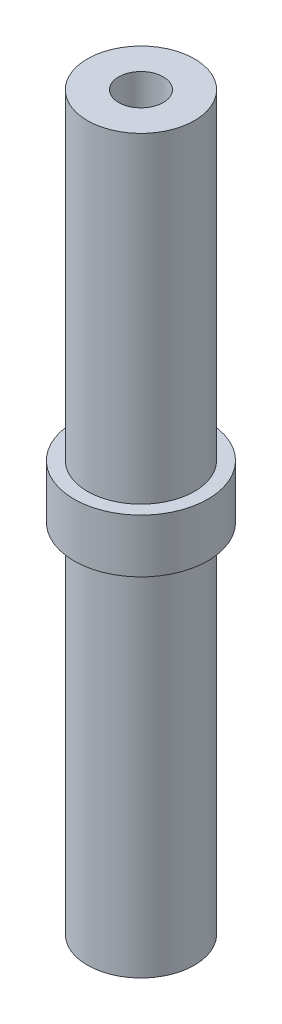
SolidWorks part; units mm, degrees
material "6061-T6 (SS)"
ref_plane "Front Plane" through (0, 0, 0) normal (0, 0, 1) x (1, 0, 0)
ref_plane "Top Plane" through (0, 0, 0) normal (0, 1, 0) x (1, 0, 0)
ref_plane "Right Plane" through (0, 0, 0) normal (1, 0, 0) x (0, 0, -1)
sketch "Sketch1" plane through (0, 0, 0) normal (0, 1, 0) x (1, 0, 0)
  circle A0 centre (0, 0) radius 3
  circle A1 centre (0, 0) radius 2 construction
  dimension "D1" = 6
  dimension "D2" = 4
extrude "Boss-Extrude1" add sketch "Sketch1" along normal blind 20.5 and the other way blind 20.5
sketch "Sketch2" plane through (0, 20.5, 0) normal (0, 1, 0) x (1, 0, 0)
  point P0 (0, 0)
hole_wizard "M3x0.5 Tapped Hole1" positions "Sketch4" profile "Sketch5" tap size "M3x0.5" standard "ANSI Metric"
sketch "Sketch4" plane through (0, 20.5, 0) normal (0, 1, 0) x (1, 0, 0)
  point P0 (0, 0)
sketch "Sketch5" plane through (0, 20.5, 0) normal (1, 0, 0) x (0, 0, 1)
  line L0 (0, 0) -> (0, 8.7511)
  line L1 (0, 8.7511) -> (1.25, 8)
  line L2 (1.25, 8) -> (1.25, 0)
  line L5 (1.25, 0) -> (0, 0)
  line L10 (0, 8.7511) -> (-1.25, 8) construction
  line L11 (0, -6.35) -> (0, 107.95) construction
  dimension "Tap Drill Dia." = 2.5
  dimension "Tap Drill Depth" = 8
  dimension "Drill Angle" = 118
cosmetic thread "Hole Thread1" parameters "D1"=6, "D2"=3
ref_plane "Plane1" through (0, -0.5, 0) normal (0, 1, 0) x (1, 0, 0)
sketch "Sketch6" plane through (0, -0.5, 0) normal (0, 1, 0) x (1, 0, 0)
  circle A0 centre (0, 0) radius 3.75
  dimension "D1" = 7.5
extrude "Boss-Extrude2" add sketch "Sketch6" along normal blind 3
mirror "Mirror1" about plane through (0, 0, 0) normal (0, 1, 0) of "M3x0.5 Tapped Hole1"
